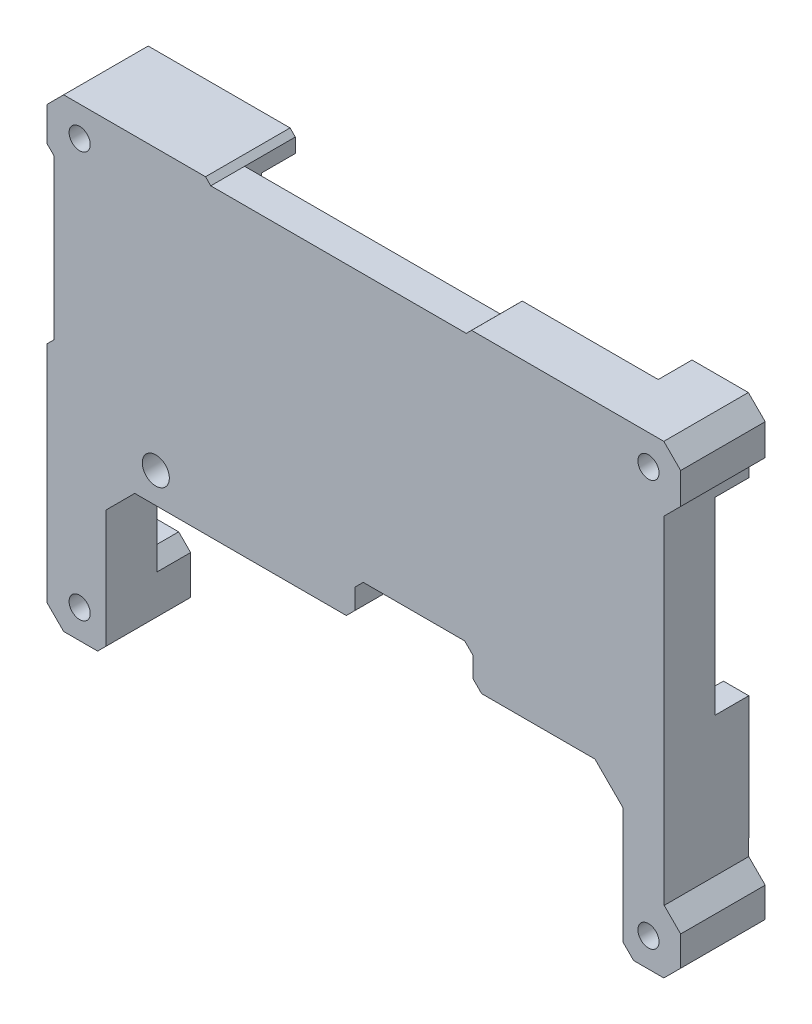
SolidWorks part; units mm, degrees
ref_plane "前视基准面" through (0, 0, 0) normal (0, 0, 1) x (1, 0, 0)
ref_plane "上视基准面" through (0, 0, 0) normal (0, 1, 0) x (1, 0, 0)
ref_plane "右视基准面" through (0, 0, 0) normal (1, 0, 0) x (0, 0, -1)
other "Configuration Table"
sketch "草图1" plane through (0, 0, 0) normal (0, 0, 1) x (1, 0, 0)
  line L1 (0, 0) -> (85, 0)
  line L2 (0, 0) -> (0, 65)
  line L3 (0, 65) -> (85, 65)
  line L4 (85, 0) -> (85, 65)
  dimension "D1" = 65
  dimension "D2" = 85
extrude "凸台-拉伸1" add sketch "草图1" along normal blind 10
sketch "草图2" plane through (0, 0, 0) normal (0, 0, -1) x (-1, 0, 0)
  circle A0 centre (-76.1669, 56.4425) radius 1.25
  circle A1 centre (-8.8888, 56.4425) radius 1.25
  circle A2 centre (-76.1669, 8.4151) radius 1.25
  circle A3 centre (-8.8888, 8.4151) radius 1.25
  dimension "D1" = 2.5
  dimension "D2" = 2.5
  dimension "D3" = 2.5
  dimension "D4" = 2.5
extrude "切除-拉伸1" cut sketch "草图2" against normal up to next
sketch "草图3" plane through (0, 0, 0) normal (0, 0, -1) x (-1, 0, 0)
  line L28 (-85, 0) -> (-85, 65) construction
  line L29 (-85, 65) -> (0, 65)
  line L30 (-85, 65) -> (-85, 0)
  line L31 (-85, 0) -> (0, 0)
  line L32 (0, 65) -> (0, 0)
  line L56 (-5, 33.4629) -> (-5.8713, 34.3342)
  line L57 (-5, 6.9926) -> (-5, 33.4629)
  line L58 (-6.9926, 5) -> (-5, 6.9926)
  line L59 (-16.2697, 5) -> (-6.9926, 5)
  line L60 (-17.4616, 6.1866) -> (-16.2697, 5)
  line L61 (-31.7436, 6.1829) -> (-17.4616, 6.1866)
  line L62 (-32.9265, 5) -> (-31.7436, 6.1829)
  line L63 (-58.7727, 5) -> (-32.9265, 5)
  line L64 (-60.0435, 6.2655) -> (-58.7727, 5)
  line L65 (-73.1524, 6.2618) -> (-60.0435, 6.2655)
  line L66 (-74.4142, 5) -> (-73.1524, 6.2618)
  line L67 (-77.9822, 5) -> (-74.4142, 5)
  line L68 (-79.9747, 6.9926) -> (-77.9822, 5)
  line L69 (-79.9747, 10.5083) -> (-79.9747, 6.9926)
  line L70 (-78.0283, 12.46) -> (-79.9747, 10.5083)
  line L71 (-78.032, 52.3531) -> (-78.0283, 12.46)
  line L72 (-79.9747, 54.2958) -> (-78.032, 52.3531)
  line L73 (-79.9747, 57.9821) -> (-79.9747, 54.2958)
  line L74 (-77.9822, 59.9747) -> (-79.9747, 57.9821)
  line L75 (-55.2451, 59.9747) -> (-77.9822, 59.9747)
  line L76 (-54.6148, 59.3497) -> (-55.2451, 59.9747)
  line L77 (-24.3949, 59.3534) -> (-54.6148, 59.3497)
  line L78 (-23.7736, 59.9747) -> (-24.3949, 59.3534)
  line L79 (-6.9926, 59.9747) -> (-23.7736, 59.9747)
  line L80 (-5, 57.9821) -> (-6.9926, 59.9747)
  line L81 (-5, 54.0174) -> (-5, 57.9821)
  line L82 (-5.875, 53.1371) -> (-5, 54.0174)
  line L83 (-5.8713, 34.3342) -> (-5.875, 53.1371)
extrude "切除-拉伸2" cut sketch "草图3" against normal up to next
sketch "草图4" plane through (0, 0, 0) normal (0, 0, -1) x (-1, 0, 0)
  line L0 (-73.1524, 6.2618) -> (-73.1524, 20.0323)
  line L1 (-73.1524, 20.0323) -> (-69.8316, 23.3532)
  line L2 (-69.8316, 23.3532) -> (-46.788, 23.3532)
  line L3 (-46.788, 23.3532) -> (-15.4038, 23.3532)
  line L4 (-15.4038, 23.3532) -> (-12.014, 19.9634)
  line L5 (-12.014, 19.9634) -> (-12.014, 6.188)
  line L6 (-31.7436, 6.1829) -> (-17.4616, 6.1866) construction
  line L7 (-12.014, 6.188) -> (-12.014, 0.194)
  line L8 (-12.014, 0.194) -> (-73.1524, 0.194)
  line L9 (-73.1524, 0.194) -> (-73.1524, 6.2618)
  line L10 (-73.1524, 6.2618) -> (-60.0435, 6.2655) construction
  point P4 (0, 0)
  point P12 (-12.014, 6.188)
  dimension "D1" = 135
  dimension "D2" = 135
  dimension "D3" = 4.7938
extrude "切除-拉伸4" cut sketch "草图4" against normal up to next
sketch "草图5" plane through (0, 0, 0) normal (0, 0, -1) x (-1, 0, 0)
  line L0 (-24.3949, 59.3534) -> (-24.3949, 53.9064)
  line L1 (-24.3949, 53.9064) -> (-25.5261, 52.7749)
  line L2 (-25.5261, 52.7749) -> (-53.4826, 52.7749)
  line L3 (-53.4826, 52.7749) -> (-54.6142, 53.9061)
  line L4 (-54.6142, 53.9061) -> (-54.6148, 59.3497)
  line L5 (-24.3949, 59.3534) -> (-54.6148, 59.3497) construction
  line L6 (-23.7736, 59.9747) -> (-24.3949, 59.3534) construction
  line L7 (-24.3949, 59.3534) -> (-54.6148, 59.3497)
  dimension "D1" = 135
  dimension "D2" = 134.993
  dimension "D3" = 1.6
  dimension "D4" = 1.6
extrude "切除-拉伸7" cut sketch "草图5" against normal blind 6
sketch "草图6" plane through (0, 0, 0) normal (0, 0, -1) x (-1, 0, 0)
  line L0 (-5.8713, 34.3342) -> (-11.6713, 34.3342)
  line L1 (-5, 33.4629) -> (-5.8713, 34.3342) construction
  line L6 (-5.8713, 34.3342) -> (-5.875, 53.1371) construction
  line L7 (-5.8735, 45.2504) -> (-5.8745, 50.3342)
  line L8 (-5.8735, 45.2504) -> (-5.8713, 34.3342)
  line L9 (-5.8745, 50.3342) -> (-11.6713, 50.3342)
  line L10 (-11.6713, 50.3342) -> (-11.6713, 34.3342)
  dimension "D1" = 5.8
  dimension "D2" = 16
extrude "切除-拉伸8" cut sketch "草图6" against normal blind 6
sketch "草图7" plane through (0, 0, 0) normal (0, 0, -1) x (-1, 0, 0)
  line L0 (-76.4321, 51.2623) -> (-74.4321, 51.2623)
  line L1 (-74.4321, 51.2623) -> (-71.3195, 54.3749)
  line L2 (-71.3195, 54.3749) -> (-71.3195, 58.3749)
  line L3 (-71.3195, 58.3749) -> (-71.3195, 59.9747)
  line L4 (-76.4321, 51.2623) -> (-78.0319, 51.2623)
  line L5 (-78.0298, 28.9377) -> (-75.0298, 28.9377)
  line L6 (-75.0298, 28.9377) -> (-75.0298, 13.9377)
  line L7 (-72.9158, 11.8236) -> (-75.0298, 13.9377)
  line L8 (-24.3949, 57.6633) -> (-23.7321, 57.6633)
  line L9 (-23.7321, 57.6633) -> (-23.0617, 58.334)
  line L10 (-23.0617, 58.334) -> (-12.072, 58.334)
  line L11 (-12.072, 58.334) -> (-12.072, 55.334)
  line L12 (-12.072, 55.334) -> (-9.875, 53.1371)
  line L13 (-9.875, 53.1371) -> (-5.875, 53.1371)
  line L14 (-6.5998, 12.014) -> (-10.5998, 12.014)
  line L15 (-10.5998, 12.014) -> (-12.014, 10.5998)
  line L16 (-12.014, 10.5998) -> (-12.014, 5)
  line L17 (-6.5998, 12.014) -> (-5, 12.014)
  line L18 (-72.9158, 11.8236) -> (-73.1524, 12.0603)
  line L37 (-5.8713, 34.3342) -> (-11.6713, 34.3342)
  line L38 (-11.6713, 34.3342) -> (-11.6713, 50.3342)
  line L39 (-11.6713, 34.3342) -> (-11.6713, 50.3342)
  line L40 (-11.6713, 50.3342) -> (-5.8745, 50.3342)
  line L41 (-11.6713, 50.3342) -> (-5.8745, 50.3342)
  line L42 (-5.8745, 50.3342) -> (-5.875, 53.1371)
  line L43 (-5.875, 53.1371) -> (-5, 54.0174)
  line L44 (-5, 54.0174) -> (-5, 57.9821)
  line L45 (-5, 57.9821) -> (-6.9926, 59.9747)
  line L46 (-6.9926, 59.9747) -> (-23.7736, 59.9747)
  line L47 (-23.7736, 59.9747) -> (-24.3949, 59.3534)
  line L48 (-24.3949, 59.3534) -> (-24.3949, 53.9064)
  line L49 (-24.3949, 53.9064) -> (-25.5261, 52.7749)
  line L50 (-25.5261, 52.7749) -> (-53.4826, 52.7749)
  line L51 (-53.4826, 52.7749) -> (-54.6142, 53.9061)
  line L52 (-54.6142, 53.9061) -> (-54.6148, 59.3497)
  line L53 (-54.6148, 59.3497) -> (-55.2451, 59.9747)
  line L54 (-55.2451, 59.9747) -> (-77.9822, 59.9747)
  line L55 (-77.9822, 59.9747) -> (-79.9747, 57.9821)
  line L56 (-79.9747, 57.9821) -> (-79.9747, 54.2958)
  line L57 (-79.9747, 54.2958) -> (-78.032, 52.3531)
  line L58 (-78.032, 52.3531) -> (-78.0283, 12.46)
  line L59 (-78.0283, 12.46) -> (-79.9747, 10.5083)
  line L60 (-79.9747, 10.5083) -> (-79.9747, 6.9926)
  line L61 (-79.9747, 6.9926) -> (-77.9822, 5)
  line L62 (-77.9822, 5) -> (-74.4142, 5)
  line L63 (-74.4142, 5) -> (-73.1524, 6.2618)
  line L64 (-73.1524, 6.2618) -> (-73.1524, 20.0323)
  line L65 (-73.1524, 20.0323) -> (-69.8316, 23.3532)
  line L66 (-69.8316, 23.3532) -> (-15.4038, 23.3532)
  line L67 (-15.4038, 23.3532) -> (-12.014, 19.9634)
  line L68 (-12.014, 19.9634) -> (-12.014, 5)
  line L70 (-12.014, 5) -> (-6.9926, 5)
  line L71 (-6.9926, 5) -> (-5, 6.9926)
  line L72 (-5, 6.9926) -> (-5, 33.4629)
  line L73 (-5, 33.4629) -> (-5.8713, 34.3342)
  line L74 (-5.8713, 34.3342) -> (-11.6713, 34.3342)
  line L79 (-5.8745, 50.3342) -> (-5.875, 53.1371)
  line L80 (-5.875, 53.1371) -> (-5, 54.0174)
  line L81 (-5, 54.0174) -> (-5, 57.9821)
  line L82 (-5, 57.9821) -> (-6.9926, 59.9747)
  line L83 (-6.9926, 59.9747) -> (-23.7736, 59.9747)
  line L84 (-23.7736, 59.9747) -> (-24.3949, 59.3534)
  line L85 (-24.3949, 59.3534) -> (-24.3949, 53.9064)
  line L86 (-24.3949, 53.9064) -> (-25.5261, 52.7749)
  line L87 (-25.5261, 52.7749) -> (-53.4826, 52.7749)
  line L88 (-53.4826, 52.7749) -> (-54.6142, 53.9061)
  line L89 (-54.6142, 53.9061) -> (-54.6148, 59.3497)
  line L90 (-54.6148, 59.3497) -> (-55.2451, 59.9747)
  line L91 (-55.2451, 59.9747) -> (-77.9822, 59.9747)
  line L92 (-77.9822, 59.9747) -> (-79.9747, 57.9821)
  line L93 (-79.9747, 57.9821) -> (-79.9747, 54.2958)
  line L94 (-79.9747, 54.2958) -> (-78.032, 52.3531)
  line L95 (-78.032, 52.3531) -> (-78.0283, 12.46)
  line L96 (-78.0283, 12.46) -> (-79.9747, 10.5083)
  line L97 (-79.9747, 10.5083) -> (-79.9747, 6.9926)
  line L98 (-79.9747, 6.9926) -> (-77.9822, 5)
  line L99 (-77.9822, 5) -> (-74.4142, 5)
  line L100 (-74.4142, 5) -> (-73.1524, 6.2618)
  line L101 (-73.1524, 6.2618) -> (-73.1524, 20.0323)
  line L102 (-73.1524, 20.0323) -> (-69.8316, 23.3532)
  line L103 (-69.8316, 23.3532) -> (-15.4038, 23.3532)
  line L104 (-15.4038, 23.3532) -> (-12.014, 19.9634)
  line L105 (-12.014, 19.9634) -> (-12.014, 5)
  line L107 (-12.014, 5) -> (-6.9926, 5)
  line L108 (-6.9926, 5) -> (-5, 6.9926)
  line L109 (-5, 6.9926) -> (-5, 33.4629)
  line L110 (-5, 33.4629) -> (-5.8713, 34.3342)
  line M51 (-5.8713, 34.3342) -> (-11.6713, 34.3342)
  line M56 (-5.8745, 50.3342) -> (-5.875, 53.1371)
  line M62 (-24.3949, 59.3534) -> (-24.3949, 53.9064)
  line M63 (-24.3949, 53.9064) -> (-25.5261, 52.7749)
  line M64 (-25.5261, 52.7749) -> (-53.4826, 52.7749)
  line M65 (-53.4826, 52.7749) -> (-54.6142, 53.9061)
  line M66 (-54.6142, 53.9061) -> (-54.6148, 59.3497)
  line M67 (-54.6148, 59.3497) -> (-55.2451, 59.9747)
  line M68 (-55.2451, 59.9747) -> (-77.9822, 59.9747)
  line M72 (-78.032, 52.3531) -> (-78.0283, 12.46)
  line M78 (-73.1524, 6.2618) -> (-73.1524, 20.0323)
  line M79 (-73.1524, 20.0323) -> (-69.8316, 23.3532)
  line M80 (-69.8316, 23.3532) -> (-15.4038, 23.3532)
  line M81 (-15.4038, 23.3532) -> (-12.014, 19.9634)
  line M82 (-12.014, 19.9634) -> (-12.014, 5)
  line M84 (-12.014, 5) -> (-6.9926, 5)
  line M86 (-5, 6.9926) -> (-5, 33.4629)
  line M87 (-5, 33.4629) -> (-5.8713, 34.3342)
  dimension "D2" = 90
  dimension "D3" = 15
  dimension "D4" = 135
  dimension "D5" = 4
  dimension "D6" = 3
  dimension "D7" = 135
  dimension "D8" = 45
  dimension "D9" = 3
  dimension "D1" = 0
extrude "切除-拉伸11" cut sketch "草图7" against normal blind 4 contours L14 L17 L13 L12 L11 L10 L9 L8 L3 L2 L1 L0 L4 L5 L6 L7 L16 L15 M86 M87 M51 M56 M62 M63 M64 M65 M66 M67 M68 M72 M78 M79 M80 M81 M82 M84 region at (42.2419, 38.4538, 0)
sketch "草图8" plane through (0, 0, 4) normal (0, 0, -1) x (-1, 0, 0)
  line L1 (-73.3481, 45.9587) -> (-65.3481, 45.9587)
  line L2 (-73.3481, 45.9587) -> (-73.3481, 40.9587)
  line L3 (-73.3481, 40.9587) -> (-65.3481, 40.9587)
  line L4 (-65.3481, 45.9587) -> (-65.3481, 40.9587)
  dimension "D1" = 5
  dimension "D2" = 8
extrude "切除-拉伸12" cut sketch "草图8" against normal blind 1
sketch "草图10" plane through (0, 0, 4) normal (0, 0, -1) x (-1, 0, 0)
  line L0 (-41.5465, 34.8898) -> (-37.5465, 34.8898)
  line L1 (-46.9465, 34.8898) -> (-41.5465, 34.8898)
  line L2 (-46.9465, 34.8898) -> (-46.9465, 28.8898)
  line L3 (-46.9465, 28.8898) -> (-41.5465, 28.8898)
  line L4 (-41.5465, 34.8898) -> (-41.5465, 28.8898)
  line L5 (-37.5465, 34.8898) -> (-32.1465, 34.8898)
  line L6 (-37.5465, 34.8898) -> (-37.5465, 28.8898)
  line L7 (-37.5465, 28.8898) -> (-32.1465, 28.8898)
  line L8 (-32.1465, 34.8898) -> (-32.1465, 28.8898)
  line L9 (-37.5465, 28.8898) -> (-41.5465, 28.8898)
  dimension "D1" = 5.4
  dimension "D2" = 6
  dimension "D3" = 5.4
  dimension "D4" = 4
extrude "凸台-拉伸2" add sketch "草图10" along normal offset from surface (2.04 mm away) 3 contours L4 L1 L2 L3 | L9 L6 L0 L4 | L8 L5 L6 L7 region at (44.2465, 31.8898, 4) region at (39.5465, 31.8898, 4) region at (34.8465, 31.8898, 4)
sketch "草图11" plane through (0, 0, 4) normal (0, 0, -1) x (-1, 0, 0)
  line L1 (-40.8318, 43.6929) -> (-36.6318, 43.6929)
  line L2 (-40.8318, 43.6929) -> (-40.8318, 38.6929)
  line L3 (-40.8318, 38.6929) -> (-36.6318, 38.6929)
  line L4 (-36.6318, 43.6929) -> (-36.6318, 38.6929)
  dimension "D1" = 4.2
  dimension "D2" = 5
extrude "凸台-拉伸3" add sketch "草图11" along normal offset from surface (1.3001 mm away) 3
sketch "草图12" plane through (0, 0, 4) normal (0, 0, -1) x (-1, 0, 0)
  line L0 (-24.6106, 30.6859) -> (-32.1465, 34.8898)
  line L1 (-30.6106, 30.6859) -> (-18.6106, 30.6859)
  line L2 (-30.6106, 30.6859) -> (-30.6106, 24.6859)
  line L3 (-30.6106, 24.6859) -> (-18.6106, 24.6859)
  line L4 (-18.6106, 30.6859) -> (-18.6106, 24.6859)
  line L5 (-32.1465, 34.8898) -> (-46.9465, 34.8898) construction
  line L6 (-32.1465, 28.8898) -> (-32.1465, 34.8898) construction
  line L7 (-32.1465, 34.8898) -> (-32.1465, 28.8898)
  line L8 (-32.1465, 28.8898) -> (-30.6106, 27.6859)
  line M47 (-32.1465, 34.8898) -> (-32.1465, 28.8898)
  dimension "D1" = 12
  dimension "D2" = 6
extrude "凸台-拉伸4" add sketch "草图12" along normal offset from surface (1.89 mm away) 3 contours L4 L1 L2 L3 | L8 L2 L1 L0 M47 region at (29.9515, 31.5919, 4) region at (24.6106, 27.6859, 4)
sketch "草图13" plane through (0, 0, 4) normal (0, 0, -1) x (-1, 0, 0)
  line L1 (-62.8902, 40.6188) -> (-59.7758, 40.6188)
  line L2 (-62.8902, 40.6188) -> (-62.8902, 35.6362)
  line L3 (-62.8902, 35.6362) -> (-59.7758, 35.6362)
  line L4 (-59.7758, 40.6188) -> (-59.7758, 35.6362)
  point P4 (-62.8613, 35.6362)
  point P5 (-59.7758, 35.666)
  point P6 (-62.8902, 35.6362)
  point P7 (0, 0)
extrude "凸台-拉伸5" add sketch "草图13" along normal offset from surface (4 mm away) 2
sketch "草图14" plane through (0, 0, 4) normal (0, 0, -1) x (-1, 0, 0)
  line L1 (-65.7408, 30.6119) -> (-59.7408, 30.6119)
  line L2 (-65.7408, 30.6119) -> (-65.7408, 23.6119)
  line L3 (-65.7408, 23.6119) -> (-59.7408, 23.6119)
  line L4 (-59.7408, 30.6119) -> (-59.7408, 23.6119)
  dimension "D1" = 7
  dimension "D2" = 6
extrude "凸台-拉伸6" add sketch "草图14" along normal offset from surface (1.89 mm away) 3
sketch "草图15" plane through (0, 0, 10) normal (0, 0, 1) x (1, 0, 0)
  line L0 (69.8316, 23.3532) -> (15.4038, 23.3532) construction
  line L1 (41.4288, 23.3532) -> (55.4288, 23.3532)
  line L2 (41.4288, 23.3532) -> (41.4288, 27.7532)
  line L3 (41.4288, 27.7532) -> (55.4288, 27.7532)
  line L4 (55.4288, 23.3532) -> (55.4288, 27.7532)
  dimension "D1" = 14
  dimension "D2" = 4.4
extrude "切除-拉伸13" cut sketch "草图15" against normal up to surface (6 mm away) up to face at (69.3481, 43.4587, 4)
chamfer "倒角1" distance 1 angle 45 5 edges at (41.4288, 23.3532, 7) (41.4288, 27.7532, 7) (55.4288, 27.7532, 7) (55.4288, 23.3532, 7) (12.014, 5, 5)
chamfer "倒角2" distance 0.6 angle 45 4 edges at (59.7758, 38.1275, 4) (61.333, 40.6188, 4) (62.8902, 38.1275, 4) (61.333, 35.6362, 4)
chamfer "倒角5" distance 0.6 angle 45 4 edges at (36.6318, 41.1929, 4) (38.7318, 38.6929, 4) (40.8318, 41.1929, 4) (38.7318, 43.6929, 4)
chamfer "倒角6" distance 0.6 angle 45 3 edges at (59.7408, 27.1119, 4) (62.7408, 30.6119, 4) (65.7408, 27.1119, 4)
sketch "草图16" plane through (0, 0, 4) normal (0, 0, -1) x (-1, 0, 0)
  circle A0 centre (-17.8941, 26.9463) radius 1.6
  dimension "D1" = 3.2
extrude "切除-拉伸14" cut sketch "草图16" against normal through all both and the other way through all
